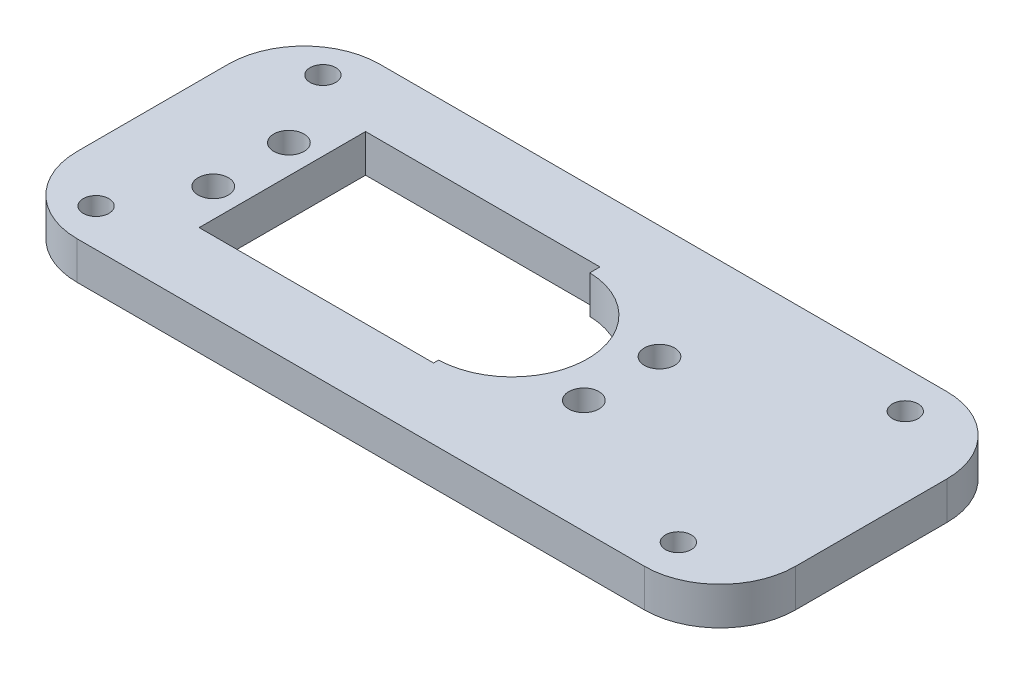
SolidWorks part; units mm, degrees
ref_plane "Front Plane" through (0, 0, 0) normal (0, 0, 1) x (1, 0, 0)
ref_plane "Top Plane" through (0, 0, 0) normal (0, 1, 0) x (1, 0, 0)
ref_plane "Right Plane" through (0, 0, 0) normal (1, 0, 0) x (0, 0, -1)
sketch "Sketch9" plane through (0, 0, 0) normal (0, 1, 0) x (1, 0, 0)
  line L1 (-47.5, 20) -> (47.5, 20)
  line L2 (-47.5, 20) -> (-47.5, -20)
  line L3 (-47.5, -20) -> (47.5, -20)
  line L4 (47.5, 20) -> (47.5, -20)
  line L5 (-47.5, 20) -> (47.5, -20) construction
  line L6 (-47.5, -20) -> (47.5, 20) construction
  point P0 (0, 0)
  dimension "D1" = 95
  dimension "D2" = 40
extrude "Boss-Extrude5" add sketch "Sketch9" along normal blind 5 separate body
sketch "Sketch10" plane through (0, 5, 0) normal (0, 1, 0) x (1, 0, 0)
  line L4 (-30.7077, 11.3457) -> (-30.711, -10.6563)
  line L5 (-30.711, -10.6563) -> (0.2923, -10.661)
  line L6 (0.2923, -10.661) -> (0.2923, 11.339)
  line L7 (0.2923, 11.339) -> (-30.7077, 11.3457)
  circle A0 centre (14.5, 5) radius 2
  circle A1 centre (14.5, -5) radius 2
  circle A2 centre (-34.5, 5) radius 2
  circle A3 centre (-34.5, -5) radius 2
  circle A4 centre (0, 0) radius 10
  circle A5 centre (-13, 0) radius 8
  point P12 (0, 0)
  point P13 (0, 0)
  point P14 (14.1008, 5.9102)
  point P22 (-4.8935, -1.1108)
  dimension "D1" = 16
  dimension "D2" = 10
  dimension "D3" = 10
  dimension "D6" = 20
  dimension "D7" = 2
  dimension "D9" = 14.5
  dimension "D10" = 34.5
  dimension "D11" = 13
  dimension "D4" = 31
  dimension "D5" = 22.002
  dimension "D8" = 14.5
  dimension "D12" = 5
  dimension "D13" = 11.339
  dimension "D14" = 30.7094
extrude "Cut-Extrude5" cut sketch "Sketch10" against normal through all contours A5 A4 L6 L7 L4 L5 | L6 A4 | A5 A4 L6 | A4 A5 | A4 A5 | A0 | A1 | A2 | A3 region at (-15.2078, 5, -10.9621) region at (4.4025, 5, 0) region at (-2.8641, 5, 0) region at (-7.5596, 5, 0) region at (-14.4547, 5, 0) region at (14.5, 5, -5) region at (14.5, 5, 5)
sketch "Sketch11" plane through (0, 5, 0) normal (0, 1, 0) x (1, 0, 0)
  circle A0 centre (-40, 15) radius 1.7
  circle A1 centre (37, 15) radius 1.7
  circle A2 centre (37, -15) radius 1.7
  circle A3 centre (-40, -15) radius 1.7
  dimension "D1" = 3.4
  dimension "D3" = 77
  dimension "D5" = 30
  dimension "D2" = 40
  dimension "D4" = 15
extrude "Cut-Extrude6" cut sketch "Sketch11" against normal through all
fillet "Fillet1" radius 10 4 edges at (47.5, 2.5, 20) (-47.5, 2.5, 20) (-47.5, 2.5, -20) (47.5, 2.5, -20)
